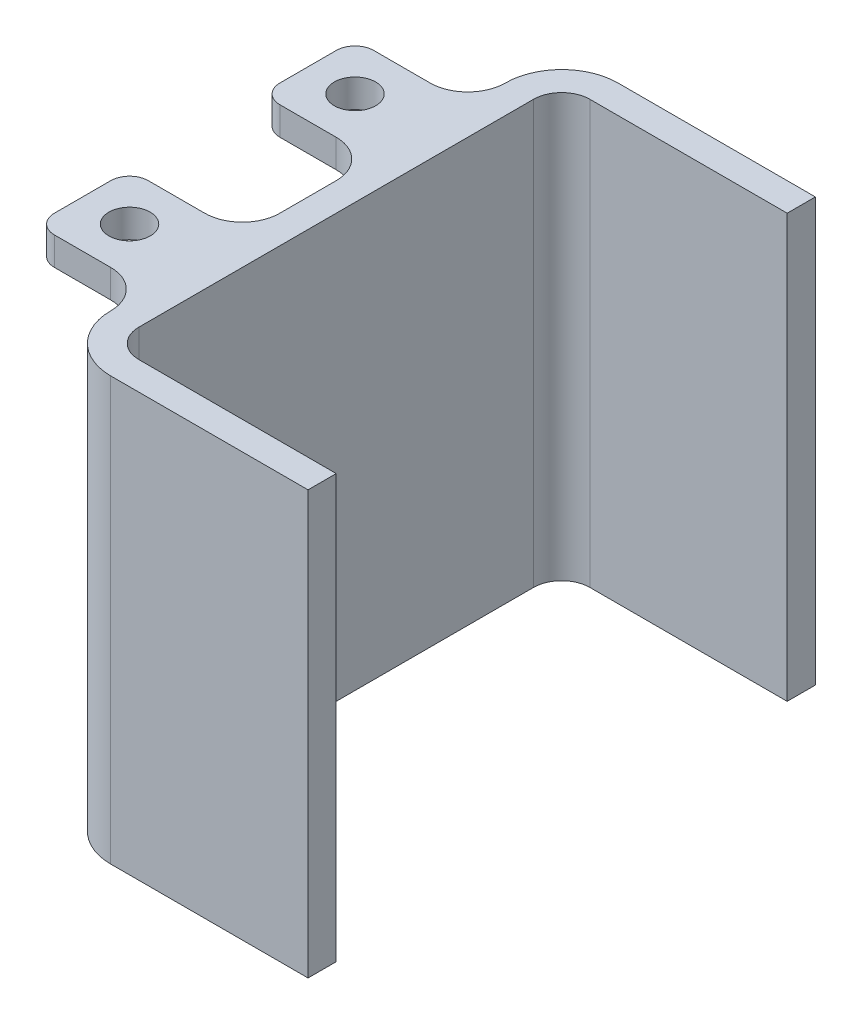
SolidWorks part; units mm, degrees
ref_plane "Front Plane" through (0, 0, 0) normal (0, 0, 1) x (1, 0, 0)
ref_plane "Top Plane" through (0, 0, 0) normal (0, 1, 0) x (1, 0, 0)
ref_plane "Right Plane" through (0, 0, 0) normal (1, 0, 0) x (0, 0, -1)
sketch "Sketch2" plane through (0, 0, 0) normal (0, 1, 0) x (1, 0, 0)
  line L0 (-6, 30) -> (6, 30)
  line L1 (6, 30) -> (6, 24)
  line L2 (6, 24) -> (2, 24)
  line L3 (2, 24) -> (2, -24)
  line L4 (2, -24) -> (6, -24)
  line L5 (6, -24) -> (6, -30)
  line L6 (6, -30) -> (-6, -30)
  line L7 (-6, -30) -> (-6, -24)
  line L8 (-6, -24) -> (-2, -24)
  line L9 (-2, -24) -> (-2, 24)
  line L10 (-2, 24) -> (-6, 24)
  line L11 (-6, 24) -> (-6, 30)
  dimension "D2" = 60
  dimension "D3" = 6
  dimension "D4" = 4
sketch "Sketch3" plane through (0, 0, 0) normal (0, 1, 0) x (1, 0, 0)
  line L5 (-8, 24) -> (-8, -24) construction
  line L6 (-8, 24) -> (-29, 24)
  line L7 (-32, 21) -> (-32, -21)
  line L8 (-29, -24) -> (-8, -24)
  line L16 (-8, 27) -> (-29, 27)
  line L17 (-35, 21) -> (-35, -21)
  line L18 (-29, -27) -> (-8, -27)
  line L19 (-8, 27) -> (-8, 24)
  line L20 (-8, -24) -> (-8, -27)
  arc A10 (-29, -24) -> (-32, -21) centre (-29, -21) cw
  arc A11 (-32, 21) -> (-29, 24) centre (-29, 21) cw
  arc A12 (-35, 21) -> (-29, 27) centre (-29, 21) cw
  arc A13 (-29, -27) -> (-35, -21) centre (-29, -21) cw
  point P2 (-8, 0)
  point P9 (-32, 24)
  dimension "D4" = 3
  dimension "D1" = 2
  dimension "D2" = 48
  dimension "D3" = 24
  dimension "D5" = 3
extrude "Boss-Extrude1" add sketch "Sketch3" along normal blind 45
sketch "Sketch4" plane through (0, 45, 0) normal (0, 1, 0) x (1, 0, 0)
  line L0 (-35, 21) -> (-35, -21) construction
  line L1 (-47, 17) -> (-35, 17)
  line L2 (-47, 17) -> (-47, 7)
  line L3 (-47, 7) -> (-35, 7)
  line L4 (-35, 17) -> (-35, 7)
  line L6 (-35, -7) -> (-47, -7)
  line L7 (-35, -7) -> (-35, -17)
  line L8 (-35, -17) -> (-47, -17)
  line L9 (-47, -7) -> (-47, -17)
  circle A0 centre (-42, 12) radius 2.2
  circle A1 centre (-42, -12) radius 2.2
  point P8 (-47, 12)
  point P15 (0, 0)
  point P16 (-47, -12)
  point P17 (0, 0)
  point P18 (-51, -16.2712)
  point P19 (0, 0)
  dimension "D2" = 4.4
  dimension "D6" = 4.4
  dimension "D1" = 5
  dimension "D3" = 12
  dimension "D4" = 10
  dimension "D5" = 10
  dimension "D7" = 12
  dimension "D8" = 12
extrude "Boss-Extrude2" add sketch "Sketch4" against normal blind 3
fillet "Fillet1" radius 4 4 edges at (-35, 43.5, 17) (-35, 43.5, 7) (-35, 43.5, -17) (-35, 43.5, -7)
fillet "Fillet2" radius 2 2 edges at (-35, 42, 12) (-35, 42, -12)
fillet "Fillet3" radius 2 4 edges at (-47, 43.5, 17) (-47, 43.5, 7) (-47, 43.5, -7) (-47, 43.5, -17)
